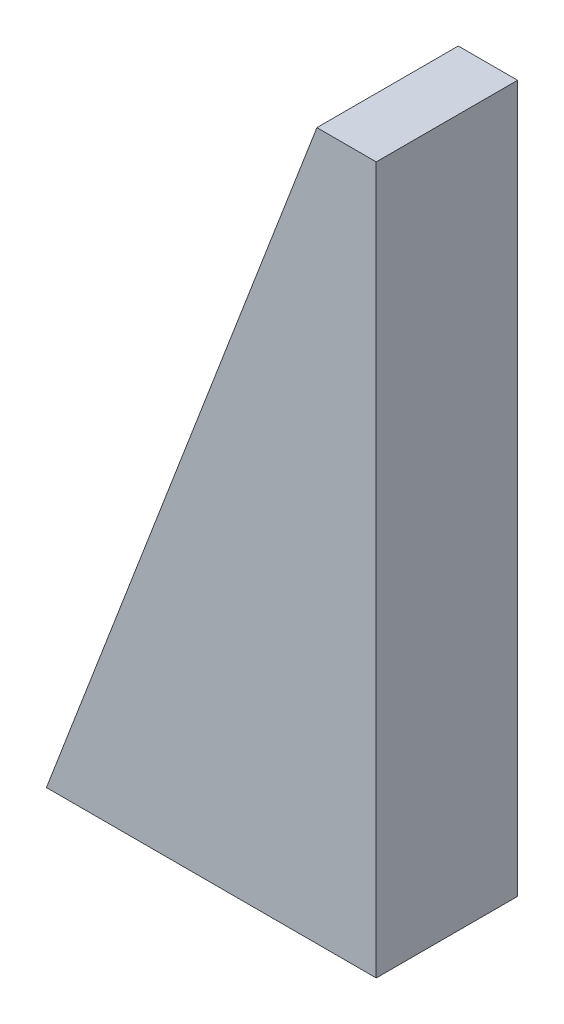
SolidWorks part; units mm, degrees
ref_plane "Front Plane" through (0, 0, 0) normal (0, 0, 1) x (1, 0, 0)
ref_plane "Top Plane" through (0, 0, 0) normal (0, 1, 0) x (1, 0, 0)
ref_plane "Right Plane" through (0, 0, 0) normal (1, 0, 0) x (0, 0, -1)
sketch "Sketch1" plane through (0, 0, 0) normal (0, 0, 1) x (1, 0, 0)
  line L0 (0, 0) -> (70, 0)
  line L1 (0, 0) -> (57.4078, 150)
  line L2 (57.4078, 150) -> (70, 150)
  line L3 (70, 150) -> (70, 0)
  dimension "D1" = 150
  dimension "D2" = 70
  dimension "D3" = 160.6103
extrude "Boss-Extrude2" add sketch "Sketch1" along normal mid plane 30 contours L3 L0 L1 L2
